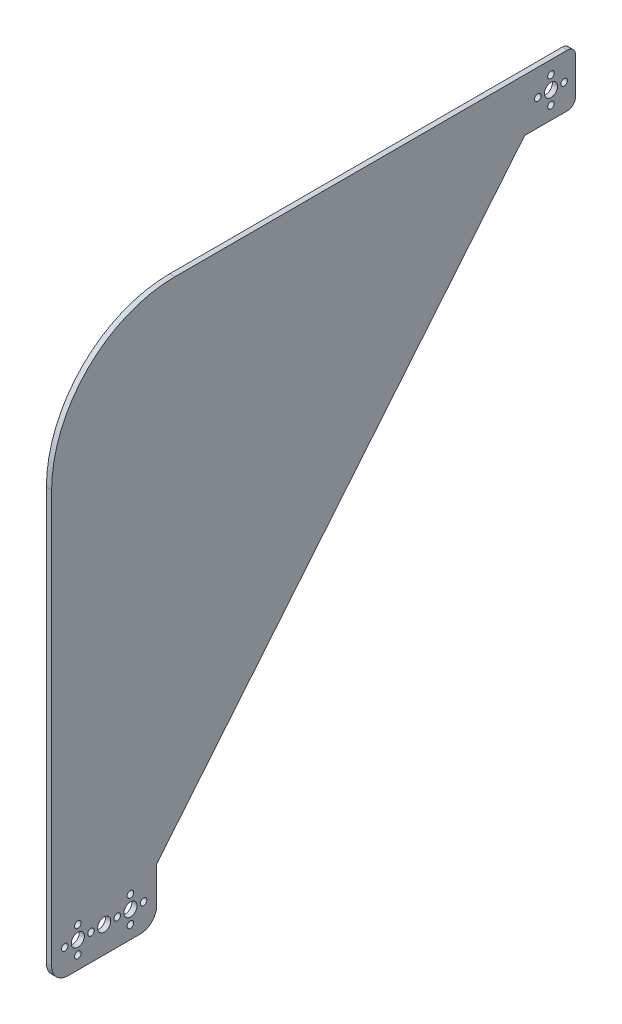
SolidWorks part; units mm, degrees
ref_plane "Front" through (0, 0, 0) normal (0, 0, 1) x (1, 0, 0)
ref_plane "Top" through (0, 0, 0) normal (0, 1, 0) x (1, 0, 0)
ref_plane "Right" through (0, 0, 0) normal (1, 0, 0) x (0, 0, -1)
sketch "Sketch1" plane through (0, 0, 0) normal (1, 0, 0) x (0, 0, -1)
  line L0 (-248, -304) -> (-264, -304) construction
  line L1 (-272, -300) -> (-272, -308) construction
  line L2 (-240, -288) -> (-240, -310)
  line L3 (-250, -320) -> (-294, -320)
  line L4 (-304, -310) -> (-304, -288)
  line L5 (-16, 16) -> (10, 16)
  line L6 (15, 11) -> (15, -11)
  line L7 (10, -16) -> (-16, -16)
  line L8 (-240, -288) -> (-16, -16)
  line L9 (-229, 16) -> (-16, 16)
  line L10 (-304, -288) -> (-304, -59)
  circle A0 centre (-256, -304) radius 4
  circle A1 centre (0, 0) radius 4
  circle A2 centre (8, 0) radius 2
  circle A3 centre (0, -8) radius 2
  circle A4 centre (-8, 0) radius 2
  circle A5 centre (0, 8) radius 2
  circle A6 centre (-248, -304) radius 2
  circle A7 centre (-256, -312) radius 2
  circle A8 centre (-264, -304) radius 2 [skipped]
  circle A9 centre (-256, -296) radius 2
  circle A10 centre (-264, -304) radius 2
  circle A11 centre (-272, -304) radius 4
  circle A12 centre (-288, -312) radius 2
  circle A13 centre (-280, -304) radius 2
  circle A14 centre (-288, -296) radius 2
  circle A15 centre (-288, -304) radius 4
  circle A16 centre (-296, -304) radius 2
  arc A17 (-240, -310) -> (-250, -320) centre (-250, -310) cw
  arc A18 (-294, -320) -> (-304, -310) centre (-294, -310) cw
  arc A19 (10, 16) -> (15, 11) centre (10, 11) cw
  arc A20 (15, -11) -> (10, -16) centre (10, -11) cw
  arc A21 (-304, -59) -> (-229, 16) centre (-229, -59) cw
  point P18 (0, 0)
  point P27 (-256, -304)
  point P47 (-272, -320)
  point P58 (15, 0)
  dimension "D1" = 8
  dimension "D4" = 4
  dimension "D14" = 10
  dimension "D15" = 5
  dimension "D19" = 75
  dimension "D2" = 256
  dimension "D3" = 304
  dimension "D5" = 8
  dimension "D7" = 8
  dimension "D10" = 16
  dimension "D11" = 16
  dimension "D12" = 16
  dimension "D13" = 16
  dimension "D16" = 15
  dimension "D17" = 16
  dimension "D18" = 16
  dimension "D9" = 2
  dimension "D6" = 4
  dimension "D8" = 4
extrude "Boss-Extrude1" add sketch "Sketch1" against normal blind 3.175
